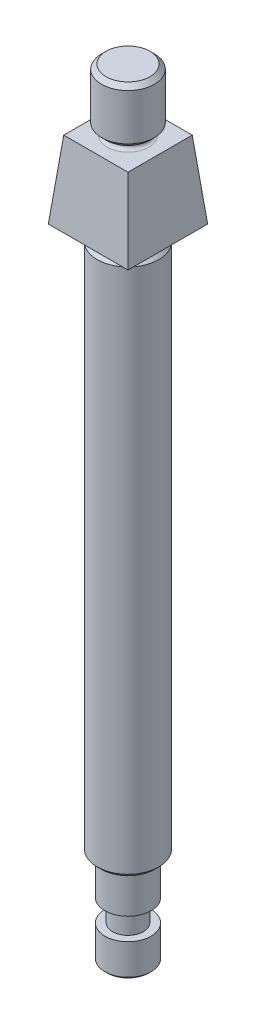
SolidWorks part; units mm, degrees
material "1.0050 (E295)"
ref_plane "Front Plane" through (0, 0, 0) normal (0, 0, 1) x (1, 0, 0)
ref_plane "Top Plane" through (0, 0, 0) normal (0, 1, 0) x (1, 0, 0)
ref_plane "Right Plane" through (0, 0, 0) normal (1, 0, 0) x (0, 0, -1)
sketch "Sketch1" plane through (0, 0, 0) normal (0, 1, 0) x (1, 0, 0)
  circle A0 centre (0, 0) radius 10.5
  dimension "D1" = 21
extrude "Boss-Extrude1" add sketch "Sketch1" along normal blind 42
sketch "Sketch3" plane through (0, 42, 0) normal (0, 1, 0) x (1, 0, 0)
  circle A0 centre (0, 0) radius 14
  dimension "D1" = 28
extrude "Boss-Extrude2" add sketch "Sketch3" along normal blind 243
sketch "Sketch4" plane through (0, 285, 0) normal (0, 1, 0) x (1, 0, 0)
  circle A0 centre (0, 0) radius 9
  dimension "D1" = 18
extrude "Boss-Extrude3" add sketch "Sketch4" along normal blind 5
sketch "Sketch5" plane through (0, 290, 0) normal (0, 1, 0) x (1, 0, 0)
  line L1 (-18.1, -18.1) -> (18.1, -18.1)
  line L2 (-18.1, -18.1) -> (-18.1, 18.1)
  line L3 (-18.1, 18.1) -> (18.1, 18.1)
  line L4 (18.1, -18.1) -> (18.1, 18.1)
  line L5 (-18.1, -18.1) -> (18.1, 18.1) construction
  line L6 (-18.1, 18.1) -> (18.1, -18.1) construction
  point P0 (0, 0)
  dimension "D1" = 36.2
  dimension "D2" = 36.2
extrude "Boss-Extrude4" add sketch "Sketch5" along normal blind 35 draft 5.711
sketch "Sketch6" plane through (0, 325, 0) normal (0, 1, 0) x (1, 0, 0)
  circle A0 centre (0, 0) radius 8
  dimension "D1" = 16
extrude "Boss-Extrude6" add sketch "Sketch6" along normal blind 3 contours A0
sketch "Sketch7" plane through (0, 328, 0) normal (0, 1, 0) x (1, 0, 0)
  circle A0 centre (0, 0) radius 12
  dimension "D1" = 24
extrude "Boss-Extrude7" add sketch "Sketch7" along normal blind 25
chamfer "Chamfer1" distance 2 angle 45 2 edges at (0, 328, 12) (0, 353, 12)
fillet "Fillet2" radius 2.5 2 edges at (0, 285, 9) (0, 290, 9)
sketch "Sketch8" plane through (0, 0, 0) normal (0, 0, 1) x (1, 0, 0)
  line L0 (-10.5, 42) -> (-10.5, 0) construction
  line L1 (-10.5, 25) -> (-7, 25)
  line L2 (-10.5, 25) -> (-10.5, 15)
  line L3 (-10.5, 15) -> (-7, 15)
  line L4 (-7, 25) -> (-7, 15)
  line L5 (-14, 42) -> (14, 42) construction
  point P6 (-10.5, 20)
  dimension "D1" = 10
  dimension "D2" = 7
  dimension "D3" = 22
revolve "Cut-Revolve1" cut sketch "Sketch8" angle 360 about axis through (0, 42, 0) along (0, -1, 0)
chamfer "Chamfer2" distance 2 angle 45 2 edges at (0, 42, 14) (0, 285, 14)
chamfer "Chamfer3" distance 1 angle 45 1 edges at (0, 0, 10.5)
fillet "Fillet3" radius 1.5 2 edges at (0, 325, 8) (0, 328, 8)
equation "\"D3@Boss-Extrude4\"=atn(0.1)"
